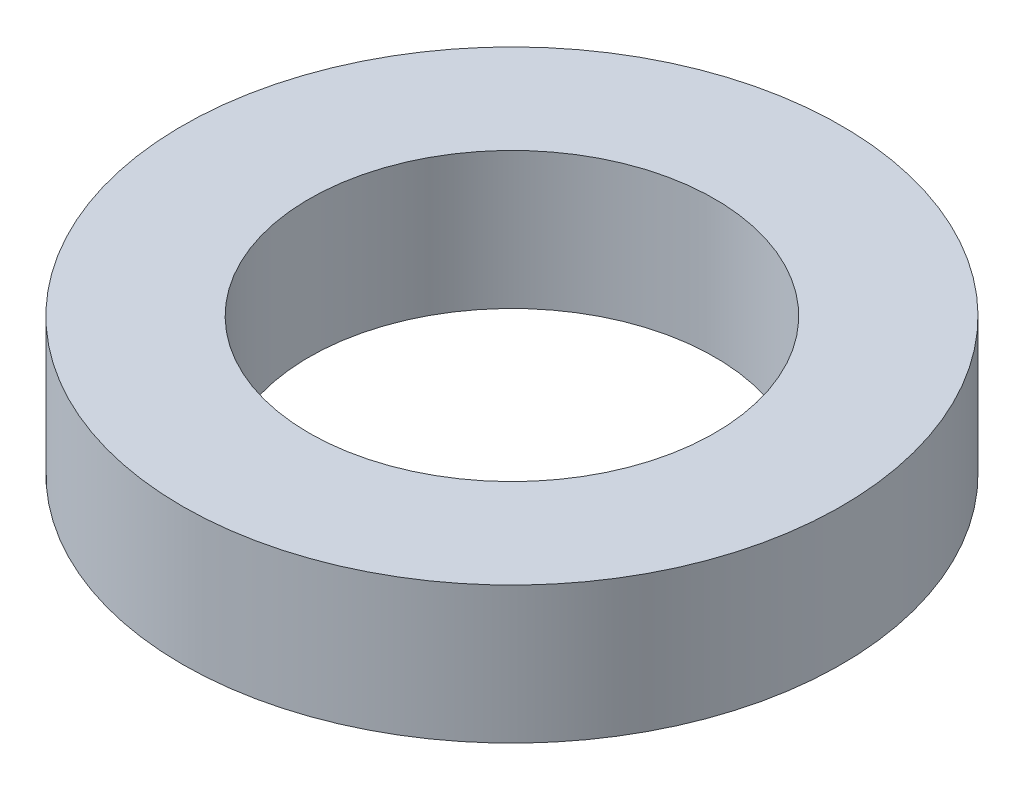
SolidWorks part; units mm, degrees
ref_plane "Front Plane" through (0, 0, 0) normal (0, 0, 1) x (1, 0, 0)
ref_plane "Top Plane" through (0, 0, 0) normal (0, 1, 0) x (1, 0, 0)
ref_plane "Right Plane" through (0, 0, 0) normal (1, 0, 0) x (0, 0, -1)
sketch "Sketch1" plane through (0, 0, 0) normal (0, 1, 0) x (1, 0, 0)
  circle A0 centre (0, 0) radius 65
  dimension "FLANGE_OD" = 130
extrude "Boss-Extrude1" add sketch "Sketch1" along normal blind 27
sketch "Sketch2" plane through (0, 0, 0) normal (0, 1, 0) x (1, 0, 0)
  circle A0 centre (0, 0) radius 40
  dimension "BORE_D" = 80
extrude "Cut-Extrude1" cut sketch "Sketch2" along normal through all
sketch "Sketch3" plane through (0, 27, 0) normal (0, 1, 0) x (1, 0, 0)
  circle A0 centre (0, 0) radius 28.6577 construction
  circle A1 centre (-28.6577, 0) radius 3.7978
  dimension "BOLT_D" = 7.5957
  dimension "BOLT_PCD" = 57.3155
extrude "Cut-Extrude2" cut sketch "Sketch3" against normal blind 23.3086 rebuild error yes
pattern_circular "CirPattern1" count 3 over 360 rebuild error yes
